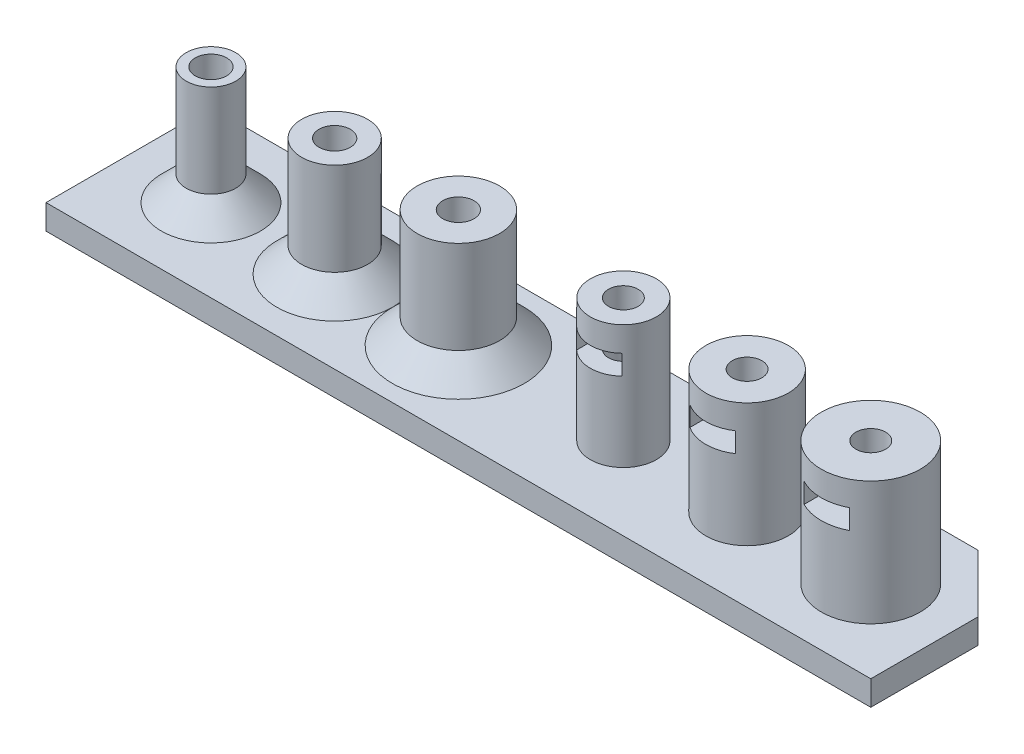
SolidWorks part; units mm, degrees
ref_plane "Front Plane" through (0, 0, 0) normal (0, 0, 1) x (1, 0, 0)
ref_plane "Top Plane" through (0, 0, 0) normal (0, 1, 0) x (1, 0, 0)
ref_plane "Right Plane" through (0, 0, 0) normal (1, 0, 0) x (0, 0, -1)
sketch "Sketch1" plane through (0, 0, 0) normal (0, 1, 0) x (1, 0, 0)
  line L1 (-50, -10) -> (50, -10)
  line L2 (-50, -10) -> (-50, 10)
  line L3 (-50, 10) -> (50, 10)
  line L4 (50, -10) -> (50, 10)
  line L5 (-50, -10) -> (50, 10) construction
  line L6 (-50, 10) -> (50, -10) construction
  point P0 (0, 0)
  dimension "D1" = 20
  dimension "D2" = 100
extrude "Boss-Extrude1" add sketch "Sketch1" along normal blind 3
sketch "Sketch2" plane through (0, 3, 0) normal (0, 1, 0) x (1, 0, 0)
  line L0 (-50, 10) -> (-50, -10) construction
  line L1 (50, 10) -> (-50, 10) construction
  circle A0 centre (-25, 0) radius 4
  circle A1 centre (-40, 0) radius 3
  circle A2 centre (-10, 0) radius 5
  circle A3 centre (-40, 0) radius 1.9
  circle A4 centre (-25, 0) radius 1.9
  circle A5 centre (-10, 0) radius 1.9
  dimension "D1" = 8
  dimension "D2" = 6
  dimension "D5" = 10
  dimension "D8" = 3.8
  dimension "D3" = 10
  dimension "D4" = 10
  dimension "D6" = 15
  dimension "D7" = 15
extrude "Boss-Extrude2" add sketch "Sketch2" along normal blind 14.25
chamfer "Chamfer1" distance 3 angle 45 1 edges at (-40, 3, -3)
chamfer "Chamfer2" distance 3 angle 45 1 edges at (-25, 3, -4)
chamfer "Chamfer3" distance 3 angle 45 1 edges at (-10, 3, -5)
sketch "Sketch14" plane through (0, 3, 0) normal (0, 1, 0) x (1, 0, 0)
  line L0 (50, -10) -> (50, 10) construction
  circle A0 centre (10, 0) radius 4
  circle A1 centre (25, 0) radius 5
  circle A2 centre (40, 0) radius 6
  circle A3 centre (10, 0) radius 1.8
  circle A4 centre (25, 0) radius 1.8
  circle A5 centre (40, 0) radius 1.8
  dimension "D1" = 8
  dimension "D2" = 10
  dimension "D3" = 12
  dimension "D7" = 3.6
  dimension "D4" = 10
  dimension "D5" = 15
  dimension "D6" = 15
extrude "Boss-Extrude3" add sketch "Sketch14" along normal blind 15
sketch "Sketch16" plane through (0, 3, 0) normal (0, 1, 0) x (1, 0, 0)
  line L0 (7.25, -1.5877) -> (7.25, -10)
  line L1 (12.75, 1.5877) -> (10, 3.1754)
  line L2 (10, 3.1754) -> (7.25, 1.5877)
  line L3 (7.25, 1.5877) -> (7.25, -1.5877)
  line L4 (12.75, -1.5877) -> (12.75, -10)
  line L6 (12.75, -1.5877) -> (12.75, 1.5877)
  line L7 (-50, -10) -> (50, -10) construction
  line L8 (7.25, -10) -> (12.75, -10)
  line L11 (11.375, -2.3816) -> (12.75, -1.5877) [skipped]
  line L12 (7.25, -1.5877) -> (8.625, -2.3816) [skipped]
  circle A0 centre (10, 0) radius 2.75 construction
  dimension "D1" = 5.5
chamfer "Chamfer4" distance 7 angle 45 1 edges at (50, 1.5, -10)
extrude "Cut-Extrude2" cut sketch "Sketch16" against normal blind 2.4 from offset 12
pattern_linear "LPattern2" count 3 spacing 15 along (1, 0, 0) of "Cut-Extrude2"
